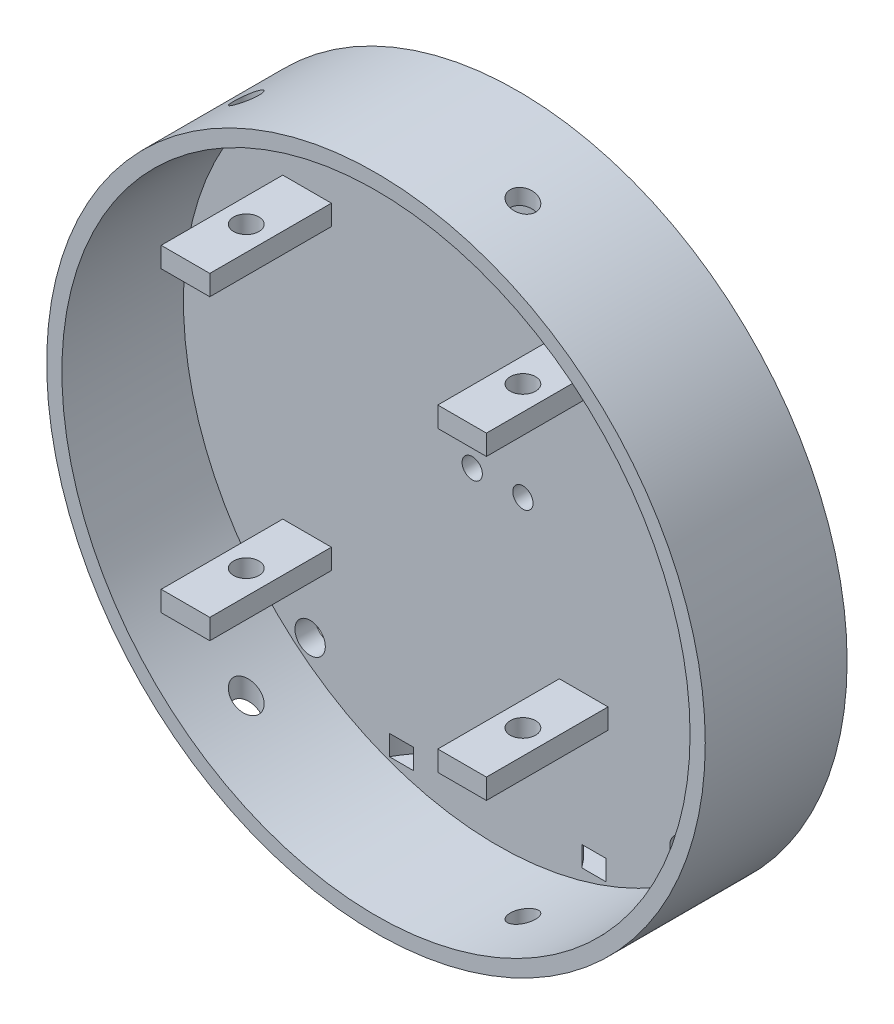
SolidWorks part; units mm, degrees
ref_plane "Alzado" through (0, 0, 0) normal (0, 0, 1) x (1, 0, 0)
ref_plane "Planta" through (0, 0, 0) normal (0, 1, 0) x (1, 0, 0)
ref_plane "Vista lateral" through (0, 0, 0) normal (1, 0, 0) x (0, 0, -1)
sketch "Croquis1" plane through (0, 0, 0) normal (0, 0, 1) x (1, 0, 0)
  line L0 (10, 20) -> (-10, 20) construction
  circle A0 centre (0, 0) radius 32.5
  circle A1 centre (-2.5, 0) radius 1
  circle A2 centre (2.5, 0) radius 1
  circle A3 centre (0, 20) radius 1
  circle A4 centre (10, 20) radius 1
  circle A5 centre (-10, 20) radius 1
  point P9 (0, 20)
  dimension "D1" = 65
  dimension "D4" = 2
  dimension "D7" = 2
  dimension "D2" = 2.5
  dimension "D3" = 2.5
  dimension "D5" = 20
  dimension "D6" = 20
extrude "Saliente-Extruir1" add sketch "Croquis1" along normal blind 2
sketch "Croquis2" plane through (0, 0, 2) normal (0, 0, 1) x (1, 0, 0)
  line L0 (-21.2, -15.7) -> (-16.4, -15.7)
  line L1 (10.9, -15.7) -> (6.1, -15.7)
  line L2 (-21.2, -15.7) -> (-21.2, -13.7)
  line L3 (-21.2, -13.7) -> (-16.4, -13.7)
  line L4 (-16.4, -13.7) -> (-16.4, -15.7)
  line L5 (6.1, -15.7) -> (6.1, -13.7)
  line L6 (6.1, -13.7) -> (10.9, -13.7)
  line L7 (10.9, -13.7) -> (10.9, -15.7)
  line L8 (6.1, -15.7) -> (10.9, -15.7)
  line L9 (0, 0) -> (12.8027, 0) construction
  line L10 (10.9, 13.7) -> (10.9, 15.7)
  line L11 (10.9, 15.7) -> (6.1, 15.7)
  line L12 (6.1, 13.7) -> (10.9, 13.7)
  line L13 (6.1, 15.7) -> (6.1, 13.7)
  line L14 (-16.4, 13.7) -> (-16.4, 15.7)
  line L15 (-21.2, 15.7) -> (-16.4, 15.7)
  line L16 (-21.2, 15.7) -> (-21.2, 13.7)
  line L17 (-21.2, 13.7) -> (-16.4, 13.7)
  point P2 (0, -15.7)
  point P3 (-16.4, -15.7)
  point P13 (8.5, -15.7)
  point P16 (8.5, 15.7)
  dimension "D1" = 32.1
  dimension "D2" = 10.9
  dimension "D3" = 15.7
  dimension "D4" = 4.8
  dimension "D5" = 4.8
  dimension "D6" = 2
  dimension "D7" = 2
extrude "Saliente-Extruir2" add sketch "Croquis2" along normal blind 12 contours L7 L6 L5 L1 | L4 L3 L2 L0 | L16 L17 L14 L15 | L11 L13 L12 L10 region at (-18.8, -14.7, 2) region at (8.5, -14.7, 2) region at (8.5, 14.7, 2) region at (-18.8, 14.7, 2)
sketch "Croquis3" plane through (0, -15.7, 0) normal (0, -1, 0) x (1, 0, 0)
  line L0 (-18.8, 14) -> (-18.8, 2) construction
  line L1 (-21.2, 14) -> (-16.4, 14) construction
  line L2 (-21.2, 2) -> (-16.4, 2) construction
  line L3 (8.5, 14) -> (8.5, 2) construction
  line L4 (10.9, 14) -> (6.1, 14) construction
  line L5 (10.9, 2) -> (6.1, 2) construction
  circle A0 centre (-18.8, 8) radius 1.25
  circle A1 centre (8.5, 8) radius 1.25
  dimension "D1" = 2.5
extrude "Cortar-Extruir1" cut sketch "Croquis3" against normal up to surface (31.4 mm away) up to face at (8.5, 15.7, 8)
ref_plane "Plano1" through (0, -32.5, 0) normal (0, -1, 0) x (-1, 0, 0)
ref_plane "Plano2" through (0, -28.75, 0) normal (0, -1, 0) x (-1, 0, 0)
sketch "Croquis5" plane through (0, -28.75, 0) normal (0, -1, 0) x (-1, 0, 0)
  line L0 (-8.5, -8) -> (18.8, -8) construction
  line L1 (0, 0) -> (0, -8) construction
  line L2 (-32.5, -2) -> (32.5, -2) construction
  line L3 (-10.68, -2) -> (-8.3104, -2)
  line L4 (32.5, 0) -> (-32.5, 0) construction
  line L5 (9.277, 0) -> (6.408, 0)
  line L6 (8.3104, -2) -> (10.68, -2)
  line L7 (-6.408, 0) -> (-9.277, 0)
  arc A0 (-9.277, 0) -> (-10.68, -2) centre (0, -8) ccw
  arc A1 (-6.408, 0) -> (-8.3104, -2) centre (0, -8) ccw
  arc A2 (10.68, -2) -> (9.277, 0) centre (0, -8) ccw
  arc A3 (8.3104, -2) -> (6.408, 0) centre (0, -8) ccw
  dimension "D1" = 24.5
  dimension "D2" = 20.5
extrude "Cortar-Extruir3" cut sketch "Croquis5" against normal blind 2
mirror "Simetría1" about plane through (0, 0, 0) normal (0, 1, 0) of "Cortar-Extruir3"
sketch "Croquis6" plane through (0, 0, 0) normal (0, 0, -1) x (-1, 0, 0)
  line L1 (-18.5, 22.5) -> (18.5, 22.5) construction
  line L2 (-18.5, 22.5) -> (-18.5, -22.5) construction
  line L3 (-18.5, -22.5) -> (18.5, -22.5) construction
  line L4 (18.5, 22.5) -> (18.5, -22.5) construction
  line L5 (-18.5, 22.5) -> (18.5, -22.5) construction
  line L6 (-18.5, -22.5) -> (18.5, 22.5) construction
  circle A0 centre (-18.5, 22.5) radius 1.5
  circle A1 centre (18.5, 22.5) radius 1.5
  circle A2 centre (18.5, -22.5) radius 1.5
  circle A3 centre (-18.5, -22.5) radius 1.5
  point P0 (0, 0)
  dimension "D3" = 3
  dimension "D1" = 45
  dimension "D2" = 37
extrude "Cortar-Extruir4" cut sketch "Croquis6" against normal blind 2.5
sketch "Croquis7" plane through (0, 0, 2) normal (0, 0, 1) x (1, 0, 0)
  circle A2 centre (0, 0) radius 32.5 construction
  circle A9 centre (0, 0) radius 32.5
  circle A11 centre (0, 0) radius 31
  dimension "D1" = 1.5
extrude "Saliente-Extruir3" add sketch "Croquis7" along normal blind 12
ref_plane "Plano3" through (0, -32.5, 0) normal (0, -1, 0) x (-1, 0, 0)
sketch "Croquis8" plane through (0, -32.5, 0) normal (0, -1, 0) x (-1, 0, 0)
  circle A0 centre (-8.5, -8) radius 1.25 construction
  circle A1 centre (-8.5, -8) radius 1.25
  circle A2 centre (18.8, -8) radius 1.25 construction
  circle A3 centre (18.8, -8) radius 1.25
extrude "Cortar-Extruir5" cut sketch "Croquis8" against normal blind 70
